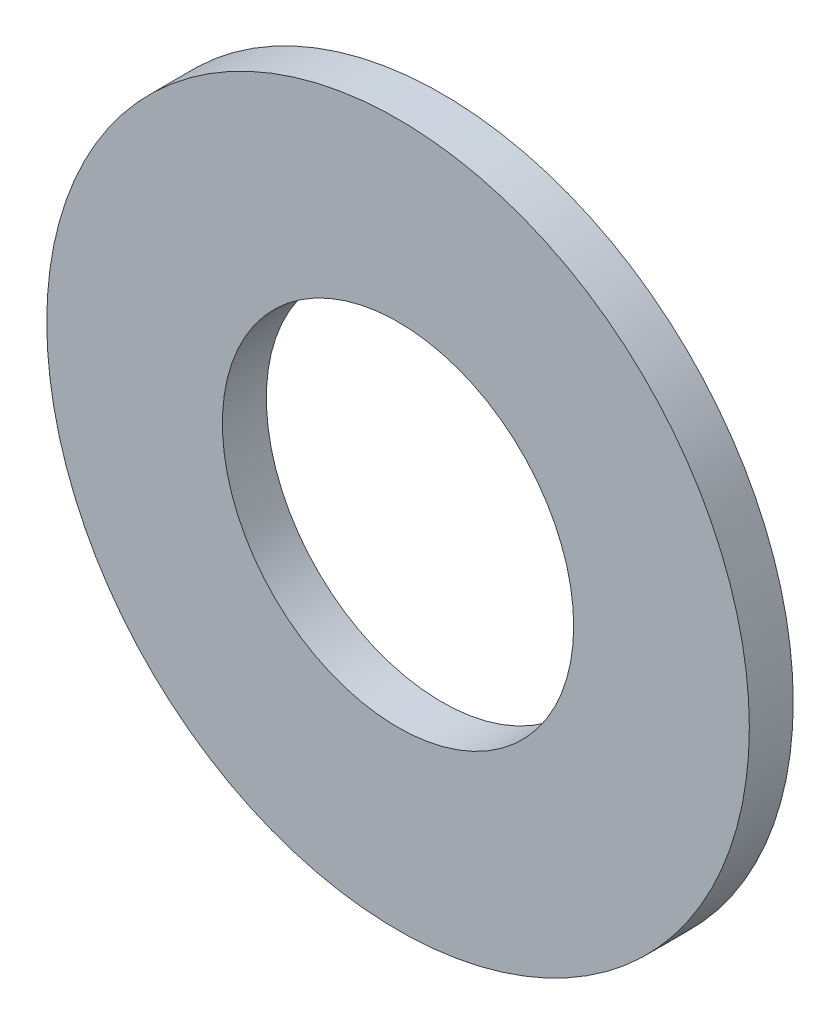
SolidWorks part; units mm, degrees
material "Nylon 101"
ref_plane "Front Plane" through (0, 0, 0) normal (0, 0, 1) x (1, 0, 0)
ref_plane "Top Plane" through (0, 0, 0) normal (0, 1, 0) x (1, 0, 0)
ref_plane "Right Plane" through (0, 0, 0) normal (1, 0, 0) x (0, 0, -1)
sketch "Sketch1" plane through (0, 0, 0) normal (0, 0, 1) x (1, 0, 0)
  circle A0 centre (0, 0) radius 6.35
  circle A1 centre (0, 0) radius 12.7
  dimension "D1" = 12.7
  dimension "D2" = 25.4
extrude "Boss-Extrude1" add sketch "Sketch1" along normal mid plane 1.5875
